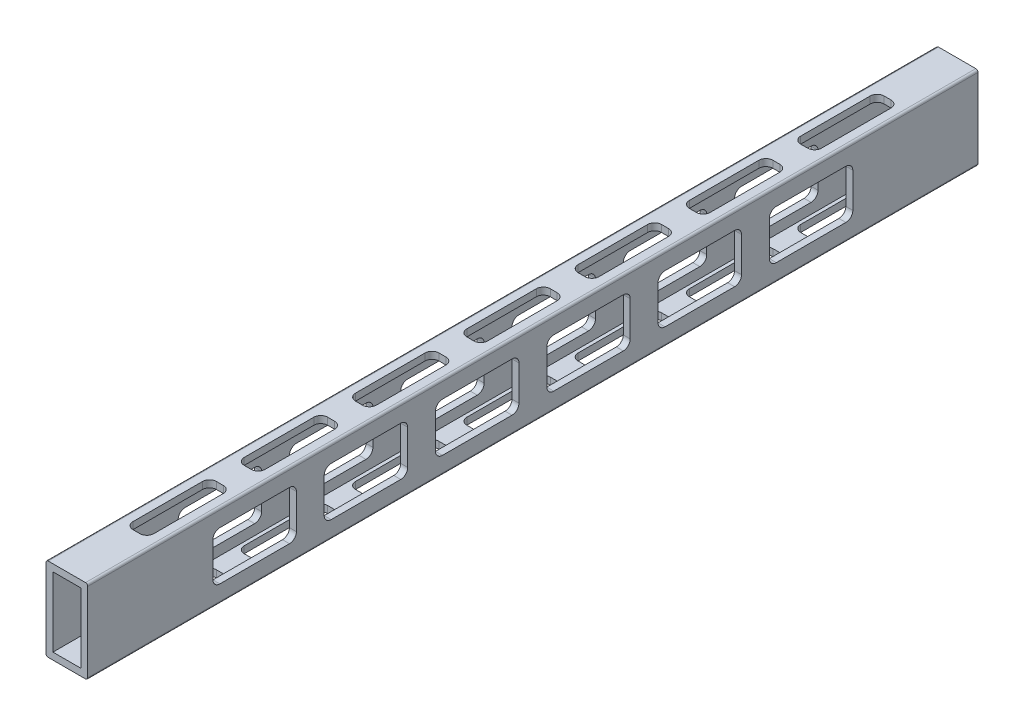
SolidWorks part; units mm, degrees
material "6061-T6 (SS)"
ref_plane "Front Plane" through (0, 0, 0) normal (0, 0, 1) x (1, 0, 0)
ref_plane "Top Plane" through (0, 0, 0) normal (0, 1, 0) x (1, 0, 0)
ref_plane "Right Plane" through (0, 0, 0) normal (1, 0, 0) x (0, 0, -1)
sketch "Sketch1" plane through (0, 0, 0) normal (0, 0, 1) x (1, 0, 0)
  line L0 (-6.35, -15.875) -> (-6.35, 15.875)
  line L1 (-8.525, -19.05) -> (8.525, -19.05)
  line L2 (-9.525, -18.05) -> (-9.525, 18.05)
  line L3 (-8.525, 19.05) -> (8.525, 19.05)
  line L4 (9.525, -18.05) -> (9.525, 18.05)
  line L5 (-9.525, -19.05) -> (9.525, 19.05) construction
  line L6 (-9.525, 19.05) -> (9.525, -19.05) construction
  line L7 (-6.35, 15.875) -> (6.35, 15.875)
  line L8 (6.35, -15.875) -> (6.35, 15.875)
  line L9 (-6.35, -15.875) -> (6.35, -15.875)
  arc A0 (-8.525, -19.05) -> (-9.525, -18.05) centre (-8.525, -18.05) cw
  arc A1 (8.525, -19.05) -> (9.525, -18.05) centre (8.525, -18.05) ccw
  arc A2 (8.525, 19.05) -> (9.525, 18.05) centre (8.525, 18.05) cw
  arc A3 (-9.525, 18.05) -> (-8.525, 19.05) centre (-8.525, 18.05) cw
  arc A4 (-6.35, 15.875) -> (-6.35, 15.875) centre (-6.35, 15.875) cw
  arc A5 (6.35, 15.875) -> (6.35, 15.875) centre (6.35, 15.875) cw
  arc A6 (6.35, -15.875) -> (6.35, -15.875) centre (6.35, -15.875) ccw
  arc A7 (-6.35, -15.875) -> (-6.35, -15.875) centre (-6.35, -15.875) cw
  point P0 (0, 0)
  dimension "D3" = 1
  dimension "D1" = 19.05
  dimension "D2" = 38.1
  dimension "D4" = 3.175
extrude "Boss-Extrude1" add sketch "Sketch1" along normal mid plane 406.4
sketch "Sketch2" plane through (0, 19.05, 0) normal (0, 1, 0) x (1, 0, 0)
  line L0 (-4.7625, -117.475) -> (-4.7625, -85.725)
  line L1 (-1.5875, -171.45) -> (1.5875, -171.45)
  line L2 (-4.7625, -168.275) -> (-4.7625, -136.525)
  line L3 (-1.5875, -133.35) -> (1.5875, -133.35)
  line L4 (4.7625, -168.275) -> (4.7625, -136.525)
  line L5 (-4.7625, -171.45) -> (4.7625, -133.35) construction
  line L6 (-4.7625, -133.35) -> (4.7625, -171.45) construction
  line L7 (-1.5875, -120.65) -> (1.5875, -120.65)
  line L8 (4.7625, -117.475) -> (4.7625, -85.725)
  line L9 (-1.5875, -82.55) -> (1.5875, -82.55)
  line L10 (-4.7625, -66.675) -> (-4.7625, -34.925)
  line L11 (-1.5875, -69.85) -> (1.5875, -69.85)
  line L12 (4.7625, -66.675) -> (4.7625, -34.925)
  line L13 (-1.5875, -31.75) -> (1.5875, -31.75)
  line L14 (-4.7625, -15.875) -> (-4.7625, 15.875)
  line L15 (-1.5875, -19.05) -> (1.5875, -19.05)
  line L16 (4.7625, -15.875) -> (4.7625, 15.875)
  line L17 (-1.5875, 19.05) -> (1.5875, 19.05)
  line L18 (-4.7625, 34.925) -> (-4.7625, 66.675)
  line L19 (-1.5875, 31.75) -> (1.5875, 31.75)
  line L20 (4.7625, 34.925) -> (4.7625, 66.675)
  line L21 (-1.5875, 69.85) -> (1.5875, 69.85)
  line L22 (0, -152.4) -> (0, -101.6) construction
  line L23 (-4.7625, 85.725) -> (-4.7625, 117.475)
  line L24 (-1.5875, 82.55) -> (1.5875, 82.55)
  line L25 (4.7625, 85.725) -> (4.7625, 117.475)
  line L26 (-1.5875, 120.65) -> (1.5875, 120.65)
  line L27 (-4.7625, 136.525) -> (-4.7625, 168.275)
  line L28 (-1.5875, 133.35) -> (1.5875, 133.35)
  line L29 (4.7625, 136.525) -> (4.7625, 168.275)
  line L30 (-1.5875, 171.45) -> (1.5875, 171.45)
  arc A0 (-1.5875, -171.45) -> (-4.7625, -168.275) centre (-1.5875, -168.275) cw
  arc A1 (1.5875, -171.45) -> (4.7625, -168.275) centre (1.5875, -168.275) ccw
  arc A2 (1.5875, -133.35) -> (4.7625, -136.525) centre (1.5875, -136.525) cw
  arc A3 (-4.7625, -136.525) -> (-1.5875, -133.35) centre (-1.5875, -136.525) cw
  arc A4 (-4.7625, -85.725) -> (-1.5875, -82.55) centre (-1.5875, -85.725) cw
  arc A5 (-1.5875, -120.65) -> (-4.7625, -117.475) centre (-1.5875, -117.475) cw
  arc A6 (1.5875, -120.65) -> (4.7625, -117.475) centre (1.5875, -117.475) ccw
  arc A7 (1.5875, -82.55) -> (4.7625, -85.725) centre (1.5875, -85.725) cw
  arc A8 (-4.7625, -34.925) -> (-1.5875, -31.75) centre (-1.5875, -34.925) cw
  arc A9 (-1.5875, -69.85) -> (-4.7625, -66.675) centre (-1.5875, -66.675) cw
  arc A10 (1.5875, -69.85) -> (4.7625, -66.675) centre (1.5875, -66.675) ccw
  arc A11 (1.5875, -31.75) -> (4.7625, -34.925) centre (1.5875, -34.925) cw
  arc A12 (-4.7625, 15.875) -> (-1.5875, 19.05) centre (-1.5875, 15.875) cw
  arc A13 (-1.5875, -19.05) -> (-4.7625, -15.875) centre (-1.5875, -15.875) cw
  arc A14 (1.5875, -19.05) -> (4.7625, -15.875) centre (1.5875, -15.875) ccw
  arc A15 (1.5875, 19.05) -> (4.7625, 15.875) centre (1.5875, 15.875) cw
  arc A16 (-4.7625, 66.675) -> (-1.5875, 69.85) centre (-1.5875, 66.675) cw
  arc A17 (-1.5875, 31.75) -> (-4.7625, 34.925) centre (-1.5875, 34.925) cw
  arc A18 (1.5875, 31.75) -> (4.7625, 34.925) centre (1.5875, 34.925) ccw
  arc A19 (1.5875, 69.85) -> (4.7625, 66.675) centre (1.5875, 66.675) cw
  arc A20 (-4.7625, 117.475) -> (-1.5875, 120.65) centre (-1.5875, 117.475) cw
  arc A21 (-1.5875, 82.55) -> (-4.7625, 85.725) centre (-1.5875, 85.725) cw
  arc A22 (1.5875, 82.55) -> (4.7625, 85.725) centre (1.5875, 85.725) ccw
  arc A23 (1.5875, 120.65) -> (4.7625, 117.475) centre (1.5875, 117.475) cw
  arc A24 (-4.7625, 168.275) -> (-1.5875, 171.45) centre (-1.5875, 168.275) cw
  arc A25 (-1.5875, 133.35) -> (-4.7625, 136.525) centre (-1.5875, 136.525) cw
  arc A26 (1.5875, 133.35) -> (4.7625, 136.525) centre (1.5875, 136.525) ccw
  arc A27 (1.5875, 171.45) -> (4.7625, 168.275) centre (1.5875, 168.275) cw
  point P0 (0, -152.4)
  point P5 (0, 0)
  point P19 (0, 101.6)
  point P20 (0, -101.6)
  point P33 (0, -50.8)
  point P46 (0, 0)
  point P59 (0, 50.8)
  point P86 (0, 152.4)
  point P99 (0, 0)
  point P100 (0, 0)
  dimension "D3" = 3.175
  dimension "D1" = 9.525
  dimension "D2" = 38.1
  dimension "D5" = 50.8
  dimension "D4" = 7
extrude "Cut-Extrude1" cut sketch "Sketch2" against normal through all both and the other way through all
sketch "Sketch3" plane through (9.525, 0, 0) normal (1, 0, 0) x (0, 0, -1)
  line L0 (-95.25, -7.9375) -> (-95.25, 7.9375)
  line L1 (-142.875, -11.1125) -> (-111.125, -11.1125)
  line L2 (-146.05, -7.9375) -> (-146.05, 7.9375)
  line L3 (-142.875, 11.1125) -> (-111.125, 11.1125)
  line L4 (-107.95, -7.9375) -> (-107.95, 7.9375)
  line L5 (-146.05, -11.1125) -> (-107.95, 11.1125) construction
  line L6 (-146.05, 11.1125) -> (-107.95, -11.1125) construction
  line L7 (-92.075, -11.1125) -> (-60.325, -11.1125)
  line L8 (-57.15, -7.9375) -> (-57.15, 7.9375)
  line L9 (-92.075, 11.1125) -> (-60.325, 11.1125)
  line L10 (-44.45, -7.9375) -> (-44.45, 7.9375)
  line L11 (-41.275, -11.1125) -> (-9.525, -11.1125)
  line L12 (-6.35, -7.9375) -> (-6.35, 7.9375)
  line L13 (-41.275, 11.1125) -> (-9.525, 11.1125)
  line L14 (-127, 0) -> (-76.2, 0) construction
  line L15 (6.35, -7.9375) -> (6.35, 7.9375)
  line L16 (9.525, -11.1125) -> (41.275, -11.1125)
  line L17 (44.45, -7.9375) -> (44.45, 7.9375)
  line L18 (9.525, 11.1125) -> (41.275, 11.1125)
  line L19 (-25.4, 0) -> (25.4, 0) construction
  line L20 (57.15, -7.9375) -> (57.15, 7.9375)
  line L21 (60.325, -11.1125) -> (92.075, -11.1125)
  line L22 (95.25, -7.9375) -> (95.25, 7.9375)
  line L23 (60.325, 11.1125) -> (92.075, 11.1125)
  line L24 (107.95, -7.9375) -> (107.95, 7.9375)
  line L25 (111.125, -11.1125) -> (142.875, -11.1125)
  line L26 (146.05, -7.9375) -> (146.05, 7.9375)
  line L27 (111.125, 11.1125) -> (142.875, 11.1125)
  arc A0 (-142.875, -11.1125) -> (-146.05, -7.9375) centre (-142.875, -7.9375) cw
  arc A1 (-111.125, -11.1125) -> (-107.95, -7.9375) centre (-111.125, -7.9375) ccw
  arc A2 (-111.125, 11.1125) -> (-107.95, 7.9375) centre (-111.125, 7.9375) cw
  arc A3 (-146.05, 7.9375) -> (-142.875, 11.1125) centre (-142.875, 7.9375) cw
  arc A4 (-95.25, 7.9375) -> (-92.075, 11.1125) centre (-92.075, 7.9375) cw
  arc A5 (-92.075, -11.1125) -> (-95.25, -7.9375) centre (-92.075, -7.9375) cw
  arc A6 (-60.325, -11.1125) -> (-57.15, -7.9375) centre (-60.325, -7.9375) ccw
  arc A7 (-60.325, 11.1125) -> (-57.15, 7.9375) centre (-60.325, 7.9375) cw
  arc A8 (-44.45, 7.9375) -> (-41.275, 11.1125) centre (-41.275, 7.9375) cw
  arc A9 (-41.275, -11.1125) -> (-44.45, -7.9375) centre (-41.275, -7.9375) cw
  arc A10 (-9.525, -11.1125) -> (-6.35, -7.9375) centre (-9.525, -7.9375) ccw
  arc A11 (-9.525, 11.1125) -> (-6.35, 7.9375) centre (-9.525, 7.9375) cw
  arc A12 (6.35, 7.9375) -> (9.525, 11.1125) centre (9.525, 7.9375) cw
  arc A13 (9.525, -11.1125) -> (6.35, -7.9375) centre (9.525, -7.9375) cw
  arc A14 (41.275, -11.1125) -> (44.45, -7.9375) centre (41.275, -7.9375) ccw
  arc A15 (41.275, 11.1125) -> (44.45, 7.9375) centre (41.275, 7.9375) cw
  arc A16 (57.15, 7.9375) -> (60.325, 11.1125) centre (60.325, 7.9375) cw
  arc A17 (60.325, -11.1125) -> (57.15, -7.9375) centre (60.325, -7.9375) cw
  arc A18 (92.075, -11.1125) -> (95.25, -7.9375) centre (92.075, -7.9375) ccw
  arc A19 (92.075, 11.1125) -> (95.25, 7.9375) centre (92.075, 7.9375) cw
  arc A20 (107.95, 7.9375) -> (111.125, 11.1125) centre (111.125, 7.9375) cw
  arc A21 (111.125, -11.1125) -> (107.95, -7.9375) centre (111.125, -7.9375) cw
  arc A22 (142.875, -11.1125) -> (146.05, -7.9375) centre (142.875, -7.9375) ccw
  arc A23 (142.875, 11.1125) -> (146.05, 7.9375) centre (142.875, 7.9375) cw
  point P0 (-127, 0)
  point P19 (25.4, 0)
  point P20 (-76.2, 0)
  point P33 (-25.4, 0)
  point P60 (76.2, 0)
  point P74 (127, 0)
  point P87 (0, 0)
  dimension "D3" = 3.175
  dimension "D1" = 22.225
  dimension "D2" = 38.1
  dimension "D5" = 50.8
  dimension "D4" = 6
extrude "Cut-Extrude2" cut sketch "Sketch3" against normal through all both and the other way through all
